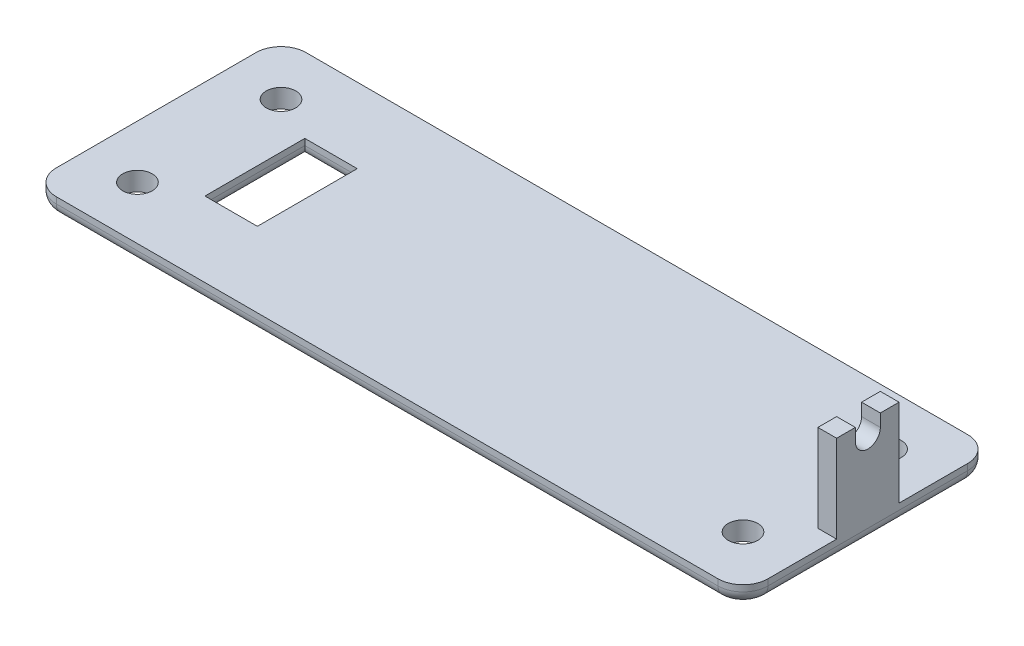
SolidWorks part; units mm, degrees
ref_plane "Front Plane" through (0, 0, 0) normal (0, 0, 1) x (1, 0, 0)
ref_plane "Top Plane" through (0, 0, 0) normal (0, 1, 0) x (1, 0, 0)
ref_plane "Right Plane" through (0, 0, 0) normal (1, 0, 0) x (0, 0, -1)
sketch "Sketch1" plane through (0, 0, 0) normal (0, 1, 0) x (1, 0, 0)
  line L1 (-72.39, -25.4) -> (72.39, -25.4)
  line L2 (-72.39, -25.4) -> (-72.39, 25.4)
  line L3 (-72.39, 25.4) -> (72.39, 25.4)
  line L4 (72.39, -25.4) -> (72.39, 25.4)
  line L5 (-72.39, -25.4) -> (72.39, 25.4) construction
  line L6 (-72.39, 25.4) -> (72.39, -25.4) construction
  point P0 (0, 0)
  dimension "D1" = 144.78
  dimension "D2" = 50.8
extrude "Boss-Extrude1" add sketch "Sketch1" along normal blind 3.81
sketch "Sketch2" plane through (0, 3.81, 0) normal (0, 1, 0) x (1, 0, 0)
  line L0 (72.39, -25.4) -> (72.39, 25.4) construction
  line L1 (72.39, 6.35) -> (68.58, 6.35)
  line L2 (72.39, 6.35) -> (72.39, -6.35)
  line L3 (72.39, -6.35) -> (68.58, -6.35)
  line L4 (68.58, 6.35) -> (68.58, -6.35)
  line L5 (72.39, 6.35) -> (68.58, 6.35) construction
extrude "Boss-Extrude2" add sketch "Sketch2" along normal blind 17.78
sketch "Sketch3" plane through (72.39, 0, 0) normal (1, 0, 0) x (0, 0, -1)
  line L0 (-2.54, 21.59) -> (2.54, 21.59)
  line L1 (-2.54, 21.59) -> (-2.54, 19.05)
  line L2 (2.54, 21.59) -> (2.54, 19.05)
  line L5 (-6.35, 21.59) -> (6.35, 21.59) construction
  arc A0 (2.54, 19.05) -> (-2.54, 19.05) centre (0, 19.05) cw
  point P5 (0, 21.59)
  dimension "D1" = 5.08
  dimension "D2" = 2.54
extrude "Cut-Extrude1" cut sketch "Sketch3" against normal up to next
sketch "Sketch4" plane through (0, 0, 0) normal (0, -1, 0) x (1, 0, 0)
  line L0 (-52.31, 25.4) -> (-52.31, -25.4) construction
  line L1 (-72.39, 25.4) -> (72.39, 25.4) construction
  line L2 (72.39, -25.4) -> (-72.39, -25.4) construction
  line L3 (-72.39, -25.4) -> (-72.39, 25.4) construction
  line L4 (-41.642, 25.4) -> (-41.642, -25.4) construction
  line L5 (-52.31, 0) -> (-41.642, 0) construction
  line L7 (-41.642, -10.16) -> (-52.31, -10.16)
  line L8 (-41.642, -10.16) -> (-41.642, 10.16)
  line L9 (-41.642, 10.16) -> (-52.31, 10.16)
  line L10 (-52.31, -10.16) -> (-52.31, 10.16)
  line L11 (-41.642, -10.16) -> (-52.31, 10.16) construction
  line L12 (-41.642, 10.16) -> (-52.31, -10.16) construction
  point P12 (-46.976, 0)
  dimension "D1" = 10.668
  dimension "D2" = 20.08
  dimension "D3" = 20.32
extrude "Cut-Extrude2" cut sketch "Sketch4" against normal through all
sketch "Sketch5" plane through (0, 0, 0) normal (0, -1, 0) x (1, 0, 0)
  line L0 (0, 25.4) -> (0, -25.4) construction
  line L1 (-72.39, 25.4) -> (72.39, 25.4) construction
  line L2 (72.39, -25.4) -> (-72.39, -25.4) construction
  line L3 (0, 0) -> (72.39, 0) construction
  line L5 (72.39, 25.4) -> (72.39, -25.4) construction
  circle A1 centre (61.595, -14.605) radius 3
  circle A2 centre (61.595, 14.605) radius 3
  circle A3 centre (-61.595, 14.605) radius 3
  circle A4 centre (-61.595, -14.605) radius 3
  dimension "D1" = 6
  dimension "D2" = 10.795
  dimension "D3" = 10.795
extrude "Cut-Extrude3" cut sketch "Sketch5" against normal through all
fillet "Fillet3" radius 5.08 4 edges at (-72.39, 1.905, -25.4) (-72.39, 1.905, 25.4) (72.39, 1.905, 25.4) (72.39, 1.905, -25.4)
fillet "Fillet4" radius 2.54 12 edges at (-72.39, 0, 0) (-70.9021, 0, 23.9121) (0, 0, 25.4) (70.9021, 0, 23.9121) (72.39, 0, 0) (70.9021, 0, -23.9121) (0, 0, -25.4) (-46.976, 0, 10.16) (-52.31, 0, 0) (-46.976, 0, -10.16) (-41.642, 0, 0) (-70.9021, 0, -23.9121)
